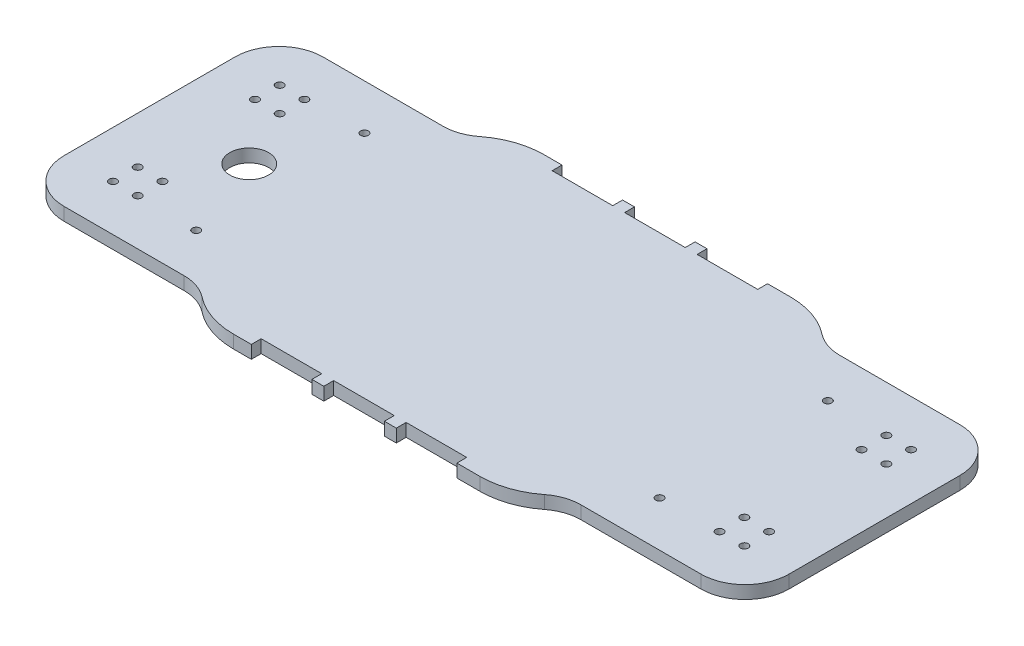
SolidWorks part; units mm, degrees
material "Acrylic (Medium-high impact)"
ref_plane "Front Plane" through (0, 0, 0) normal (0, 0, 1) x (1, 0, 0)
ref_plane "Top Plane" through (0, 0, 0) normal (0, 1, 0) x (1, 0, 0)
ref_plane "Right Plane" through (0, 0, 0) normal (1, 0, 0) x (0, 0, -1)
sketch "Sketch1" plane through (0, 0, 0) normal (0, 1, 0) x (1, 0, 0)
  line L0 (0, 60) -> (0, -60) construction
  line L1 (-140, 60) -> (140, 60) construction
  line L2 (-140, 60) -> (-140, -60) construction
  line L3 (-140, -60) -> (140, -60) construction
  line L4 (140, 60) -> (140, -60) construction
  line L5 (-140, 0) -> (140, 0) construction
  line L6 (-140, 50) -> (-140, -50)
  line L7 (-140, -50) -> (-70, -50)
  line L8 (-70, -50) -> (-70, -60)
  line L9 (-70, -60) -> (70, -60)
  line L10 (70, -60) -> (70, -50)
  line L11 (70, -50) -> (140, -50)
  line L12 (140, -50) -> (140, 50)
  line L13 (140, 50) -> (70, 50)
  line L14 (70, 50) -> (70, 60)
  line L15 (70, 60) -> (-70, 60)
  line L16 (-70, 60) -> (-70, 50)
  line L17 (-70, 50) -> (-140, 50)
  point P8 (0, 0)
  dimension "D1" = 120
  dimension "D2" = 280
  dimension "D3" = 0
  dimension "D4" = 10
  dimension "D5" = 70
  dimension "D6" = 10
  dimension "D7" = 70
  dimension "D8" = 10
  dimension "D9" = 10
  dimension "D10" = 70
  dimension "D11" = 70
sketch "Sketch4" plane through (0, 0, 0) normal (0, 1, 0) x (1, 0, 0)
  line L0 (-121.933, 32.193) -> (-112.387, 32.193) construction
  line L1 (-121.933, 32.193) -> (-121.933, 22.647) construction
  circle A1 centre (-121.933, 32.193) radius 1.5
  circle A2 centre (-112.387, 32.193) radius 1.5
  circle A3 centre (-112.387, 22.647) radius 1.5
  circle A4 centre (-121.933, 22.647) radius 1.5
  dimension "D1" = 121.933
  dimension "D2" = 32.193
  dimension "D4" = 3
  dimension "D3" = 13.5
  dimension "D7" = 90
  dimension "D5" = 2
  dimension "D6" = 2
extrude "Boss-Extrude1" add sketch "Sketch1" along normal blind 5
extrude "Cut-Extrude1" cut sketch "Sketch4" along normal up to next
mirror "Mirror1" about plane through (0, 0, 0) normal (0, 0, 1) of "Cut-Extrude1"
mirror "Mirror2" about plane through (0, 0, 0) normal (1, 0, 0) of "Mirror1", "Cut-Extrude1"
fillet "Fillet1" radius 17 1 edges at (-140, 2.5, 50)
fillet "Fillet2" radius 17 1 edges at (-140, 2.5, -50)
fillet "Fillet3" radius 17 1 edges at (140, 2.5, -50)
fillet "Fillet4" radius 17 1 edges at (140, 2.5, 50)
fillet "Fillet7" radius 30 1 edges at (-70, 2.5, -60)
fillet "Fillet8" radius 30 1 edges at (70, 2.5, -60)
fillet "Fillet9" radius 30 1 edges at (70, 2.5, 60)
fillet "Fillet10" radius 17 2 edges at (70, 2.5, -50) (70, 2.5, 50)
fillet "Fillet11" radius 17 1 edges at (-70, 2.5, -50)
fillet "Fillet12" radius 30 1 edges at (-70, 2.5, 60)
fillet "Fillet13" radius 17 1 edges at (-70, 2.5, 50)
sketch "Sketch6" plane through (0, 0, 0) normal (0, -1, 0) x (1, 0, 0)
  line L0 (0, 60) -> (0, 32.5) construction
  line L1 (-89.5, 32.5) -> (89.5, 32.5) construction
  line L2 (-89.5, 32.5) -> (-89.5, -32.5) construction
  line L3 (-89.5, -32.5) -> (89.5, -32.5) construction
  line L4 (89.5, 32.5) -> (89.5, -32.5) construction
  line L5 (-47.6393, 60) -> (47.6393, 60) construction
  line L6 (-89.5, 0) -> (-140, 0) construction
  line L7 (-140, -33) -> (-140, 33) construction
  circle A0 centre (-89.5, 32.5) radius 1.5
  circle A1 centre (-89.5, -32.5) radius 1.5
  circle A2 centre (89.5, 32.5) radius 1.5
  circle A3 centre (89.5, -32.5) radius 1.5
  dimension "D5" = 3
  dimension "D6" = 3
  dimension "D7" = 3
  dimension "D8" = 3
  dimension "D1" = 179
  dimension "D2" = 65
  dimension "D3" = 90
  dimension "D4" = 90
extrude "Cut-Extrude2" cut sketch "Sketch6" against normal up to next
sketch "Sketch8" plane through (0, 5, 0) normal (0, 1, 0) x (1, 0, 0)
  line L0 (0, 0) -> (-101.5, 0) construction
  circle A0 centre (-101.5, 0) radius 7.5
  circle A4 centre (-89.5, 32.5) radius 1.5 construction
  dimension "D1" = 15
  dimension "D2" = 12
extrude "Cut-Extrude4" cut sketch "Sketch8" against normal through all
sketch "Sketch10" plane through (0, 5, 0) normal (0, 1, 0) x (1, 0, 0)
  line L0 (-47.6393, -60) -> (47.6393, -60) construction
  line L1 (-47.6393, -60) -> (47.6393, -60) construction
  line L2 (-40.6893, -60) -> (-40.6893, -56.2)
  line L3 (-40.6893, -56.2) -> (-31.2893, -56.2) construction
  line L4 (-31.2893, -56.2) -> (-31.2893, -60) construction
  line L5 (-31.2893, -60) -> (-26.6893, -60) construction
  line L6 (-26.6893, -60) -> (-26.6893, -56.2) construction
  line L7 (-26.6893, -56.2) -> (-17.2893, -56.2) construction
  line L8 (-17.2893, -56.2) -> (-17.2893, -60) construction
  line L9 (-17.2893, -60) -> (-12.6893, -60) construction
  line L10 (-12.6893, -60) -> (-12.6893, -56.2) construction
  line L11 (-12.6893, -56.2) -> (-3.2893, -56.2) construction
  line L12 (-3.2893, -56.2) -> (-3.2893, -60) construction
  line L13 (-3.2893, -60) -> (1.3107, -60) construction
  line L14 (1.3107, -60) -> (1.3107, -56.2) construction
  line L15 (1.3107, -56.2) -> (10.7107, -56.2) construction
  line L16 (10.7107, -56.2) -> (10.7107, -60) construction
  line L17 (10.7107, -60) -> (15.3107, -60) construction
  line L18 (15.3107, -60) -> (15.3107, -56.2) construction
  line L19 (15.3107, -56.2) -> (24.7107, -56.2) construction
  line L20 (24.7107, -56.2) -> (24.7107, -60) construction
  line L21 (24.7107, -60) -> (29.3107, -60) construction
  line L22 (29.3107, -60) -> (29.3107, -56.2) construction
  line L23 (29.3107, -56.2) -> (38.7107, -56.2) construction
  line L24 (38.7107, -56.2) -> (38.7107, -60)
  line L25 (38.7107, -60) -> (38.7107, -65)
  line L26 (38.7107, -65) -> (-40.6893, -65)
  line L27 (-40.6893, -65) -> (-40.6893, -60)
  line L28 (-47.6393, -60) -> (-47.6393, -56.2) construction
  line L29 (-47.6393, -56.2) -> (47.6393, -56.2) construction
  line L30 (47.6393, -56.2) -> (47.6393, -60) construction
  line L31 (-40.6893, -56.2) -> (-17.2893, -56.2)
  line L32 (-17.2893, -56.2) -> (-17.2893, -60)
  line L33 (-17.2893, -60) -> (-12.6893, -60)
  line L34 (-12.6893, -60) -> (-12.6893, -56.2)
  line L35 (-12.6893, -56.2) -> (10.7107, -56.2)
  line L36 (10.7107, -56.2) -> (10.7107, -60)
  line L37 (10.7107, -60) -> (15.3107, -60)
  line L38 (15.3107, -60) -> (15.3107, -56.2)
  line L39 (15.3107, -56.2) -> (38.7107, -56.2)
  dimension "D1" = 6.95
  dimension "D2" = 9.4
  dimension "D3" = 4.6
  dimension "D4" = 9.4
  dimension "D5" = 4.6
  dimension "D6" = 9.4
  dimension "D7" = 4.6
  dimension "D8" = 9.4
  dimension "D9" = 4.6
  dimension "D10" = 9.4
  dimension "D11" = 4.6
  dimension "D12" = 9.4
  dimension "D13" = 3.8
  dimension "D14" = 5
extrude "Cut-Extrude5" cut sketch "Sketch10" against normal through all
mirror "Mirror3" about plane through (0, 0, 0) normal (0, 0, 1) of "Cut-Extrude5"
